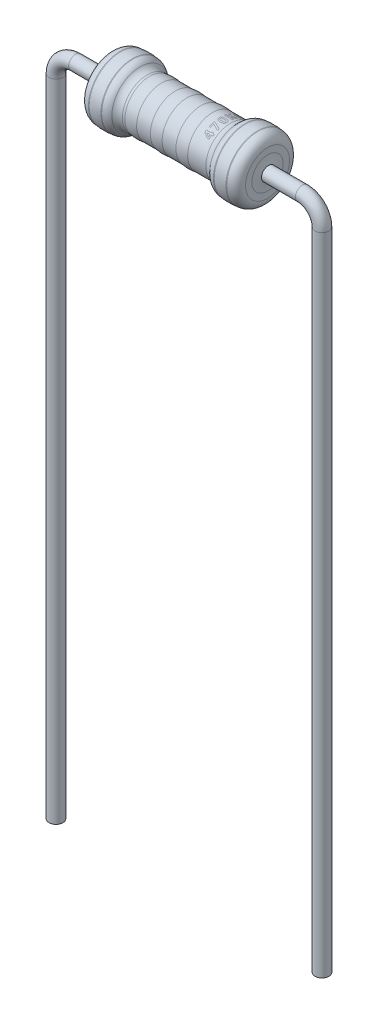
SolidWorks part; units mm, degrees
material "Plain Carbon Steel"
ref_plane "Front Plane" through (0, 0, 0) normal (0, 0, 1) x (1, 0, 0)
ref_plane "Top Plane" through (0, 0, 0) normal (0, 1, 0) x (1, 0, 0)
ref_plane "Right Plane" through (0, 0, 0) normal (1, 0, 0) x (0, 0, -1)
sketch "Sketch1" plane through (0, 0, 0) normal (0, 0, 1) x (1, 0, 0)
  line L0 (-4.33, 0) -> (4.33, 0)
  line L1 (-5.08, -0.75) -> (-5.08, -25.4)
  line L2 (5.08, -0.75) -> (5.08, -25.4)
  line L3 (-5.08, -25.4) -> (5.08, -25.4) construction
  line L4 (0, 0) -> (0, -25.4) construction
  arc A0 (-4.33, 0) -> (-5.08, -0.75) centre (-4.33, -0.75) ccw
  arc A1 (4.33, 0) -> (5.08, -0.75) centre (4.33, -0.75) cw
  dimension "D2" = 0.75
  dimension "D1" = 10.16
  dimension "D3" = 25.4
ref_plane "Plane1" through (-5.08, -25.4, 0) normal (0, -1, 0) x (-1, 0, 0)
sketch "Sketch2" plane through (-5.08, -25.4, 0) normal (0, -1, 0) x (-1, 0, 0)
  circle A0 centre (0, 0) radius 0.265
  dimension "D1" = 0.53
sweep "Sweep1" add profiles "Sketch2" path "Sketch1"
sketch "Sketch3" plane through (0, 0, 0) normal (0, 0, 1) x (1, 0, 0)
  line L0 (-3, 0) -> (3, 0)
  line L5 (-3, 0) -> (-3, 1.2)
  line L6 (3, 0) -> (3, 1.2)
  line L7 (-3, 1.2) -> (-1.8, 1.2)
  line L8 (3, 1.2) -> (1.8, 1.2)
  line L9 (-1.8, 1.2) -> (-1.8, 0.95)
  line L10 (-1.8, 0.95) -> (1.8, 0.95)
  line L11 (1.8, 0.95) -> (1.8, 1.2)
  line L12 (0, 0) -> (0, 0.95) construction
  dimension "D1" = 6
  dimension "D2" = 1.2
  dimension "D3" = 3.6
  dimension "D4" = 0.95
  dimension "D5" = 0.25
revolve "Revolve1" add sketch "Sketch3" angle 360 about L0
fillet "Fillet-1" radius 0.35 2 edges at (1.8, 0, 1.2) (-1.8, 0, 1.2)
fillet "Fillet-2" radius 0.36 4 edges at (3, 0, 1.2) (-3, 0, 1.2) (1.8, 0, 0.95) (-1.8, 0, 0.95)
sketch "Sketch5" plane through (0, 0, 0) normal (0, 0, 1) x (1, 0, 0)
  line L0 (-2.64, -1.2) -> (-2.1354, -1.2) construction
  line L5 (-2.3877, -1.2) -> (-2.3877, 0) construction
  line L10 (-3, 1.2) -> (-1.8, 1.2) construction
  line L15 (-1.05, 0.95) -> (-0.525, 0.95) construction
  line L16 (-3, 0) -> (3, 0) construction
  line L17 (-2.6127, 1.2) -> (-2.1627, 1.2) construction
  line L18 (-2.6127, 1.2) -> (-2.6127, 0) construction
  line L19 (-2.6127, 0) -> (-2.1627, 0) construction
  line L20 (-2.1627, 1.2) -> (-2.1627, 0) construction
  line L21 (-1.8, 0.95) -> (1.8, 0.95) construction
  line L22 (2.6127, 1.2) -> (2.1627, 1.2) construction
  line L23 (2.6127, 1.2) -> (2.6127, 0) construction
  line L24 (2.6127, 0) -> (2.1627, 0) construction
  line L25 (2.1627, 1.2) -> (2.1627, 0) construction
  line L26 (-1.05, 0.95) -> (-1.5, 0.95) construction
  line L27 (-1.05, 0.95) -> (-1.05, 0) construction
  line L28 (-1.05, 0) -> (-1.5, 0) construction
  line L29 (-1.5, 0.95) -> (-1.5, 0) construction
  line L30 (-2.3877, 1.2) -> (-2.3877, 1.22) construction
  line L31 (-0.075, 0.95) -> (-0.525, 0.95) construction
  line L32 (-0.075, 0.95) -> (-0.075, 0) construction
  line L33 (-0.075, 0) -> (-0.525, 0) construction
  line L34 (-0.525, 0.95) -> (-0.525, 0) construction
  line L35 (-1.275, 0.95) -> (-1.275, 0.97) construction
  line L36 (-0.3, 0.95) -> (-0.3, 0.97) construction
  line L37 (2.3877, 1.2) -> (2.3877, 1.22) construction
  line L39 (2.1354, -1.2) -> (2.64, -1.2) construction
  line L41 (2.3877, -1.2) -> (2.3877, 0) construction
  line L44 (3, 1.2) -> (1.8, 1.2) construction
  line L46 (-0.075, 0.95) -> (0.45, 0.95) construction
  line L48 (-3, 0) -> (-3, 0.6)
  line L49 (-3, 0) -> (-3, 1.2) construction
  line L50 (-3, 0) -> (-3.05, 0)
  line L51 (-3.05, 0) -> (-3.05, 0.2)
  line L52 (3, 0) -> (3.05, 0)
  line L53 (3.05, 0) -> (3.05, 0.2)
  line L54 (3, 0) -> (3, 0.6)
  line L55 (3, 0) -> (3, 1.2) construction
  line L56 (-1.05, 0) -> (-0.525, 0) construction
  line L58 (-0.075, 0) -> (0.45, 0) construction
  line L59 (0.45, 0) -> (0.45, 0.95) construction
  line L60 (0.45, 0) -> (0.9, 0) construction
  line L61 (0.9, 0) -> (0.9, 0.95) construction
  line L62 (1.5946, 0.95) -> (-1.5946, 0.95) construction
  line L63 (0.9, 0.95) -> (0.45, 0.95) construction
  line L64 (0.675, 0.95) -> (0.675, 0.97) construction
  arc A0 (-2.6127, 1.2) -> (-2.1627, 1.2) centre (-2.3877, -0.0556) cw construction
  arc A1 (-1.5, 0.95) -> (-1.05, 0.95) centre (-1.275, -0.3056) cw construction
  arc A2 (-0.525, 0.95) -> (-0.075, 0.95) centre (-0.3, -0.3056) cw construction
  arc A3 (2.1627, 1.2) -> (2.6127, 1.2) centre (2.3877, -0.0556) cw construction
  arc A6 (-3, 0.6) -> (-3.05, 0.2) centre (-4.625, 0.6) cw
  arc A7 (3.05, 0.2) -> (3, 0.6) centre (4.625, 0.6) cw
  arc A8 (0.45, 0.95) -> (0.9, 0.95) centre (0.675, -0.3056) cw construction
  dimension "D4" = 0.02
  dimension "D5" = 0.05
  dimension "D7" = 0.6
  dimension "D2" = 1.5
  dimension "D3" = 2.4
  dimension "D1" = 0.45
  dimension "D6" = 0.2
revolve "Revolve Ends" add sketch "Sketch5" angle 360 about L19
sketch "Sketch12" plane through (0, 0, 0) normal (0, 0, 1) x (1, 0, 0)
  line L0 (-2.6127, 0) -> (-2.1627, 0) construction
  line L1 (-2.6127, 0) -> (-2.1627, 0)
  line L2 (-2.6127, 1.2) -> (-2.6127, 0) construction
  line L3 (-2.6127, 1.2) -> (-2.6127, 0)
  line L4 (-2.1627, 1.2) -> (-2.1627, 0) construction
  line L5 (-2.1627, 1.2) -> (-2.1627, 0)
  arc A0 (-2.1627, 1.2) -> (-2.6127, 1.2) centre (-2.3877, -0.0556) ccw construction
  arc A1 (-2.1627, 1.2) -> (-2.6127, 1.2) centre (-2.3877, -0.0556) ccw
revolve "Revolve BAND 1" add sketch "Sketch12" angle 360 about L19
sketch "Sketch7" plane through (0, 0, 0) normal (0, 0, 1) x (1, 0, 0)
  line L0 (-1.05, 0) -> (-1.5, 0) construction
  line L1 (-1.05, 0.95) -> (-1.05, 0) construction
  line L2 (-1.5, 0.95) -> (-1.5, 0) construction
  line L3 (-1.05, 0.95) -> (-1.05, 0)
  line L4 (-1.5, 0.95) -> (-1.5, 0)
  line L5 (-1.05, 0) -> (-1.5, 0)
  arc A0 (-1.05, 0.95) -> (-1.5, 0.95) centre (-1.275, -0.3056) ccw construction
  arc A1 (-1.05, 0.95) -> (-1.5, 0.95) centre (-1.275, -0.3056) ccw
revolve "Revolve BAND 2" add sketch "Sketch7" angle 360 about L28
sketch "Sketch8" plane through (0, 0, 0) normal (0, 0, 1) x (1, 0, 0)
  line L0 (-0.075, 0.95) -> (-0.075, 0) construction
  line L1 (-0.075, 0) -> (-0.525, 0) construction
  line L2 (-0.525, 0.95) -> (-0.525, 0) construction
  line L3 (-0.075, 0.95) -> (-0.075, 0)
  line L4 (-0.075, 0) -> (-0.525, 0)
  line L5 (-0.525, 0.95) -> (-0.525, 0)
  arc A0 (-0.075, 0.95) -> (-0.525, 0.95) centre (-0.3, -0.3056) ccw construction
  arc A1 (-0.075, 0.95) -> (-0.525, 0.95) centre (-0.3, -0.3056) ccw
revolve "Revolve BAND 3" add sketch "Sketch8" angle 360 about L33
sketch "Sketch9" plane through (0, 0, 0) normal (0, 0, 1) x (1, 0, 0)
  line L0 (0.9, 0) -> (0.9, 0.95) construction
  line L1 (0.45, 0) -> (0.45, 0.95) construction
  line L2 (0.45, 0) -> (0.9, 0) construction
  line L3 (0.9, 0) -> (0.9, 0.95)
  line L4 (0.45, 0) -> (0.45, 0.95)
  line L5 (0.45, 0) -> (0.9, 0)
  arc A0 (0.9, 0.95) -> (0.45, 0.95) centre (0.675, -0.3056) ccw construction
  arc A1 (0.9, 0.95) -> (0.45, 0.95) centre (0.675, -0.3056) ccw
revolve "Revolve BAND 4" add sketch "Sketch9" angle 360 about L60
sketch "Sketch11" plane through (0, 0, 0) normal (0, 0, 1) x (1, 0, 0)
  line L0 (2.6127, 1.2) -> (2.6127, 0) construction
  line L1 (2.1627, 1.2) -> (2.1627, 0) construction
  line L2 (2.6127, 0) -> (2.1627, 0) construction
  line L3 (2.6127, 1.2) -> (2.6127, 0)
  line L4 (2.1627, 1.2) -> (2.1627, 0)
  line L5 (2.6127, 0) -> (2.1627, 0)
  arc A0 (2.6127, 1.2) -> (2.1627, 1.2) centre (2.3877, -0.0556) ccw construction
  arc A1 (2.6127, 1.2) -> (2.1627, 1.2) centre (2.3877, -0.0556) ccw
revolve "Revolve5" add sketch "Sketch11" angle 360 about L24
ref_plane "Plane2" through (0, 2, 0) normal (0, 1, 0) x (1, 0, 0)
sketch "Sketch6" plane through (0, 2, 0) normal (0, 1, 0) x (1, 0, 0)
  line L0 (0, 0) -> (1.5, 0) construction
  line L1 (1.5, 1) -> (1.5, -1) construction
  text T0 "470KΩ" font "Calibri" height 0.3
  dimension "D1" = 1.5
  dimension "D2" = 2
wrap "Wrap1" sketch "Sketch6" wrap type scribe source sketch "Sketch6" face at (1.5946, 0, 0.95)
